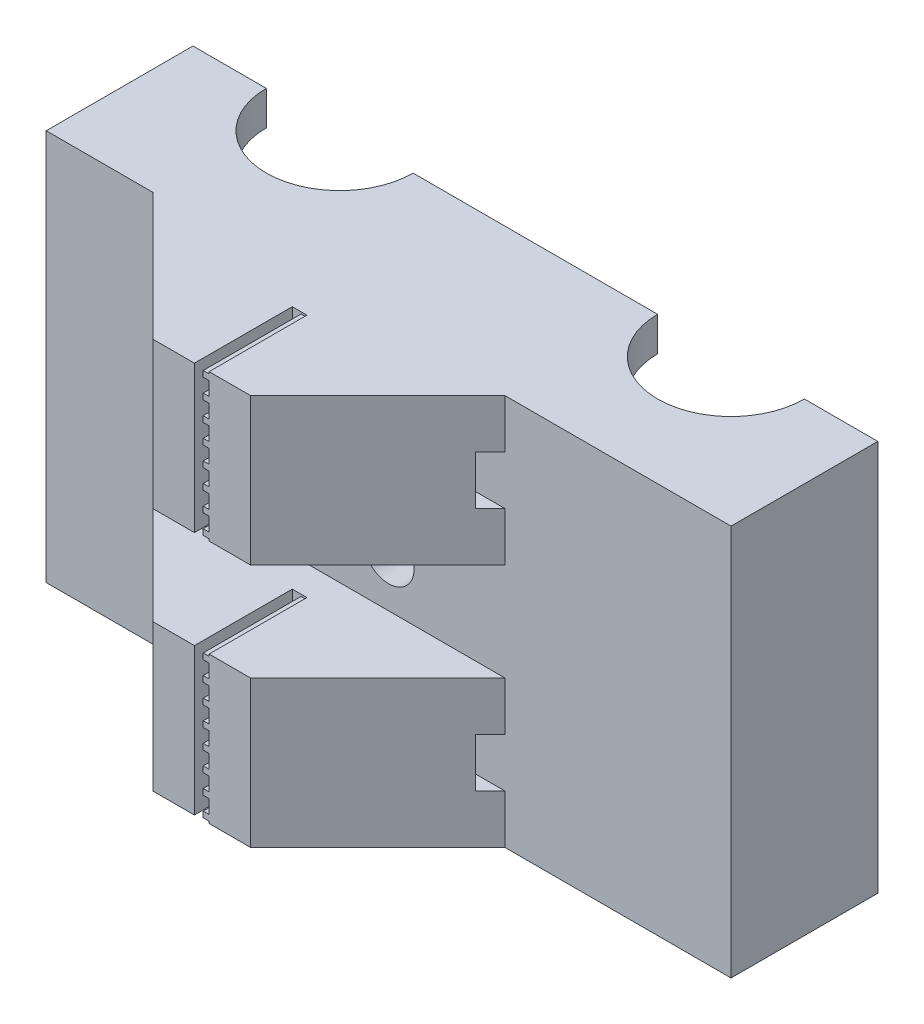
SolidWorks part; units mm, degrees
ref_plane "Front Plane" through (0, 0, 0) normal (0, 0, 1) x (1, 0, 0)
ref_plane "Top Plane" through (0, 0, 0) normal (0, 1, 0) x (1, 0, 0)
ref_plane "Right Plane" through (0, 0, 0) normal (1, 0, 0) x (0, 0, -1)
sketch "Sketch1" plane through (0, 0, 0) normal (0, 0, 1) x (1, 0, 0)
  line L1 (-35, 20) -> (35, 20)
  line L2 (-35, 20) -> (-35, -20)
  line L3 (-35, -20) -> (35, -20)
  line L4 (35, 20) -> (35, -20)
  dimension "D1" = 70
  dimension "D2" = 40
  dimension "D3" = 20
  dimension "D4" = 35
extrude "Boss-Extrude1" add sketch "Sketch1" along normal blind 15
sketch "Sketch2" plane through (0, -20, 0) normal (0, -1, 0) x (1, 0, 0)
  line L0 (-35, 0) -> (35, 0) construction
  line L1 (35, 15) -> (35, 0) construction
  circle A0 centre (-20, 0) radius 7.5
  circle A1 centre (20, 0) radius 7.5
  dimension "D1" = 15
  dimension "D2" = 15
  dimension "D5" = 40
  dimension "D6" = 15
extrude "Cut-Extrude1" cut sketch "Sketch2" against normal through all
sketch "Sketch3" plane through (0, 0, 0) normal (0, 1, 0) x (1, 0, 0)
  circle A0 centre (-20, 0) radius 11.5
  circle A1 centre (20, 0) radius 11.5
  arc A2 (12.5, 0) -> (27.5, 0) centre (20, 0) ccw construction
  arc A3 (-27.5, 0) -> (-12.5, 0) centre (-20, 0) ccw construction
  dimension "D4" = 0
  dimension "D1" = 23
  dimension "D2" = 23
  dimension "D3" = 40
  dimension "D5" = 0
extrude "Cut-Extrude2" cut sketch "Sketch3" against normal mid plane 33
sketch "Sketch4" plane through (0, 0, 15) normal (0, 0, 1) x (1, 0, 0)
  circle A0 centre (0, 0) radius 2.6
  dimension "D1" = 5.2
extrude "Cut-Extrude3" cut sketch "Sketch4" against normal through all
sketch "Sketch5" plane through (0, 0, 15) normal (0, 0, 1) x (1, 0, 0)
  line L2 (35, 20) -> (-35, 20) construction
  line L3 (-1.1, 20) -> (-11.1, 20)
  line L4 (-1.1, 20) -> (-1.1, 5)
  line L6 (-1.1, 5) -> (-11.1, 5)
  line L8 (-11.1, 20) -> (-11.1, 5)
  line L9 (-35, -20) -> (35, -20) construction
  line L10 (-1.1, -20) -> (-11.1, -20)
  line L11 (-1.1, -20) -> (-1.1, -5)
  line L12 (-1.1, -5) -> (-11.1, -5)
  line L13 (-11.1, -20) -> (-11.1, -5)
  dimension "D6" = 15
  dimension "D1" = 10
  dimension "D2" = 1.1
  dimension "D3" = 1.1
  dimension "D4" = 10
  dimension "D5" = 15
extrude "Boss-Extrude2" add sketch "Sketch5" along normal blind 3
sketch "Sketch8" plane through (0, 0, 18) normal (0, 0, 1) x (1, 0, 0)
  line L0 (-11.1, 5) -> (-1.1, 5) construction
  line L1 (-11.1, 20) -> (-6.85, 20)
  line L2 (-11.1, 20) -> (-11.1, 5)
  line L3 (-11.1, 5) -> (-6.85, 5)
  line L4 (-6.85, 20) -> (-6.85, 5)
  line L5 (-11.1, -20) -> (-1.1, -20) construction
  line L6 (-1.1, 20) -> (-5.35, 20)
  line L7 (-1.1, 20) -> (-1.1, 5)
  line L8 (-1.1, 5) -> (-5.35, 5)
  line L9 (-5.35, 20) -> (-5.35, 5)
  line L10 (-11.1, -5) -> (-6.85, -5)
  line L11 (-11.1, -5) -> (-11.1, -20)
  line L12 (-11.1, -20) -> (-6.85, -20)
  line L13 (-6.85, -5) -> (-6.85, -20)
  line L15 (-1.1, -5) -> (-5.35, -5)
  line L16 (-1.1, -5) -> (-1.1, -20)
  line L17 (-1.1, -20) -> (-5.35, -20)
  line L18 (-5.35, -5) -> (-5.35, -20)
  dimension "D1" = 4.25
  dimension "D2" = 4.25
  dimension "D3" = 4.25
  dimension "D4" = 4.25
extrude "Boss-Extrude5" add sketch "Sketch8" along normal blind 10
sketch "Sketch9" plane through (0, 0, 18) normal (0, 0, 1) x (1, 0, 0)
  line L0 (-5.35, 20) -> (-5.35, 5) construction
  line L1 (-5.35, 19.8) -> (-5.95, 19.8)
  line L2 (-5.35, 19.8) -> (-5.35, 19.2)
  line L3 (-5.35, 19.2) -> (-5.95, 19.2)
  line L4 (-5.95, 19.8) -> (-5.95, 19.2)
  line L5 (-5.35, 20) -> (-6.85, 20) construction
  line L6 (-5.35, 17.8) -> (-5.95, 17.8)
  line L7 (-5.35, 17.8) -> (-5.35, 17.2)
  line L8 (-5.35, 17.2) -> (-5.95, 17.2)
  line L9 (-5.95, 17.8) -> (-5.95, 17.2)
  line L10 (-5.35, 15.8) -> (-5.95, 15.8)
  line L11 (-5.35, 15.8) -> (-5.35, 15.2)
  line L12 (-5.35, 15.2) -> (-5.95, 15.2)
  line L13 (-5.95, 15.8) -> (-5.95, 15.2)
  line L14 (-5.35, 13.8) -> (-5.95, 13.8)
  line L15 (-5.35, 13.8) -> (-5.35, 13.2)
  line L16 (-5.35, 13.2) -> (-5.95, 13.2)
  line L17 (-5.95, 13.8) -> (-5.95, 13.2)
  line L18 (-5.35, 11.8) -> (-5.95, 11.8)
  line L19 (-5.35, 11.8) -> (-5.35, 11.2)
  line L20 (-5.35, 11.2) -> (-5.95, 11.2)
  line L21 (-5.95, 11.8) -> (-5.95, 11.2)
  line L22 (-5.35, 9.8) -> (-5.95, 9.8)
  line L23 (-5.35, 9.8) -> (-5.35, 9.2)
  line L24 (-5.35, 9.2) -> (-5.95, 9.2)
  line L25 (-5.95, 9.8) -> (-5.95, 9.2)
  line L26 (-5.35, 7.8) -> (-5.95, 7.8)
  line L27 (-5.35, 7.8) -> (-5.35, 7.2)
  line L28 (-5.35, 7.2) -> (-5.95, 7.2)
  line L29 (-5.95, 7.8) -> (-5.95, 7.2)
  line L30 (-5.35, 5.8) -> (-5.95, 5.8)
  line L31 (-5.35, 5.8) -> (-5.35, 5.2)
  line L32 (-5.35, 5.2) -> (-5.95, 5.2)
  line L33 (-5.95, 5.8) -> (-5.95, 5.2)
  line L34 (-5.35, -5) -> (-5.35, -20) construction
  line L35 (-5.35, -19.8) -> (-5.95, -19.8)
  line L36 (-5.35, -19.8) -> (-5.35, -19.2)
  line L37 (-5.35, -19.2) -> (-5.95, -19.2)
  line L38 (-5.95, -19.8) -> (-5.95, -19.2)
  line L39 (-6.85, -20) -> (-5.35, -20) construction
  line L40 (-5.35, -17.8) -> (-5.95, -17.8)
  line L41 (-5.35, -17.8) -> (-5.35, -17.2)
  line L42 (-5.35, -17.2) -> (-5.95, -17.2)
  line L43 (-5.95, -17.8) -> (-5.95, -17.2)
  line L44 (-5.35, -15.8) -> (-5.95, -15.8)
  line L45 (-5.35, -15.8) -> (-5.35, -15.2)
  line L46 (-5.35, -15.2) -> (-5.95, -15.2)
  line L47 (-5.95, -15.8) -> (-5.95, -15.2)
  line L48 (-5.35, -13.8) -> (-5.95, -13.8)
  line L49 (-5.35, -13.8) -> (-5.35, -13.2)
  line L50 (-5.35, -13.2) -> (-5.95, -13.2)
  line L51 (-5.95, -13.8) -> (-5.95, -13.2)
  line L52 (-5.35, -11.8) -> (-5.95, -11.8)
  line L53 (-5.35, -11.8) -> (-5.35, -11.2)
  line L54 (-5.35, -11.2) -> (-5.95, -11.2)
  line L55 (-5.95, -11.8) -> (-5.95, -11.2)
  line L56 (-5.35, -9.8) -> (-5.95, -9.8)
  line L57 (-5.35, -9.8) -> (-5.35, -9.2)
  line L58 (-5.35, -9.2) -> (-5.95, -9.2)
  line L59 (-5.95, -9.8) -> (-5.95, -9.2)
  line L60 (-5.35, -7.8) -> (-5.95, -7.8)
  line L61 (-5.35, -7.8) -> (-5.35, -7.2)
  line L62 (-5.35, -7.2) -> (-5.95, -7.2)
  line L63 (-5.95, -7.8) -> (-5.95, -7.2)
  line L64 (-5.35, -5.8) -> (-5.95, -5.8)
  line L65 (-5.35, -5.8) -> (-5.35, -5.2)
  line L66 (-5.35, -5.2) -> (-5.95, -5.2)
  line L67 (-5.95, -5.8) -> (-5.95, -5.2)
  dimension "D1" = 0.6
  dimension "D2" = 0.6
  dimension "D3" = 0.2
  dimension "D5" = 0.6
  dimension "D6" = 0.6
  dimension "D7" = 0.2
  dimension "D4" = 8
  dimension "D8" = 8
extrude "Boss-Extrude6" add sketch "Sketch9" along normal blind 10
chamfer "Chamfer1" distance 13 angle 45 1 edges at (-1.1, -12.5, 15)
chamfer "Chamfer2" distance 13 angle 45 1 edges at (-1.1, 12.5, 15)
chamfer "Chamfer3" distance 13 angle 45 1 edges at (-11.1, 12.5, 15)
chamfer "Chamfer4" distance 13 angle 45 1 edges at (-11.1, -12.5, 15)
sketch "Sketch10" plane through (-35, 0, 0) normal (-1, 0, 0) x (0, 0, 1)
  line L0 (15, 20) -> (15, -20) construction
  line L1 (15, 15) -> (16.5, 15)
  line L2 (15, 15) -> (15, 10)
  line L3 (15, 10) -> (16.5, 10)
  line L4 (16.5, 15) -> (16.5, 10)
  line L5 (15, -20) -> (15, -5) construction
  line L6 (15, -10) -> (16.5, -10)
  line L7 (15, -10) -> (15, -15)
  line L8 (15, -15) -> (16.5, -15)
  line L9 (16.5, -10) -> (16.5, -15)
  line L10 (28, 5) -> (15, 5) construction
  line L11 (15, -5) -> (28, -5) construction
  dimension "D1" = 1.5
  dimension "D2" = 1.5
  dimension "D3" = 5
  dimension "D4" = 5
  dimension "D5" = 5
  dimension "D6" = 5
extrude "Cut-Extrude4" cut sketch "Sketch10" against normal through all
equation "\"D3@Sketch1\"=\"D2@Sketch1\"/2"
equation "\"D4@Sketch1\"=\"D1@Sketch1\"/2"
equation "\"D2@Sketch2\"=\"D1@Sketch2\""
equation "\"D2@Sketch3\"=\"D1@Sketch3\""
equation "\"D4@Sketch5\"=\"D1@Sketch5\""
equation "\"D3@Sketch5\"=\"D2@Sketch5\""
equation "\"D6@Sketch5\"=\"D5@Sketch5\""
equation "\"D2@Sketch8\"=\"D1@Sketch8\""
equation "\"D3@Sketch8\"=\"D1@Sketch8\""
equation "\"D4@Sketch8\"=\"D1@Sketch8\""
